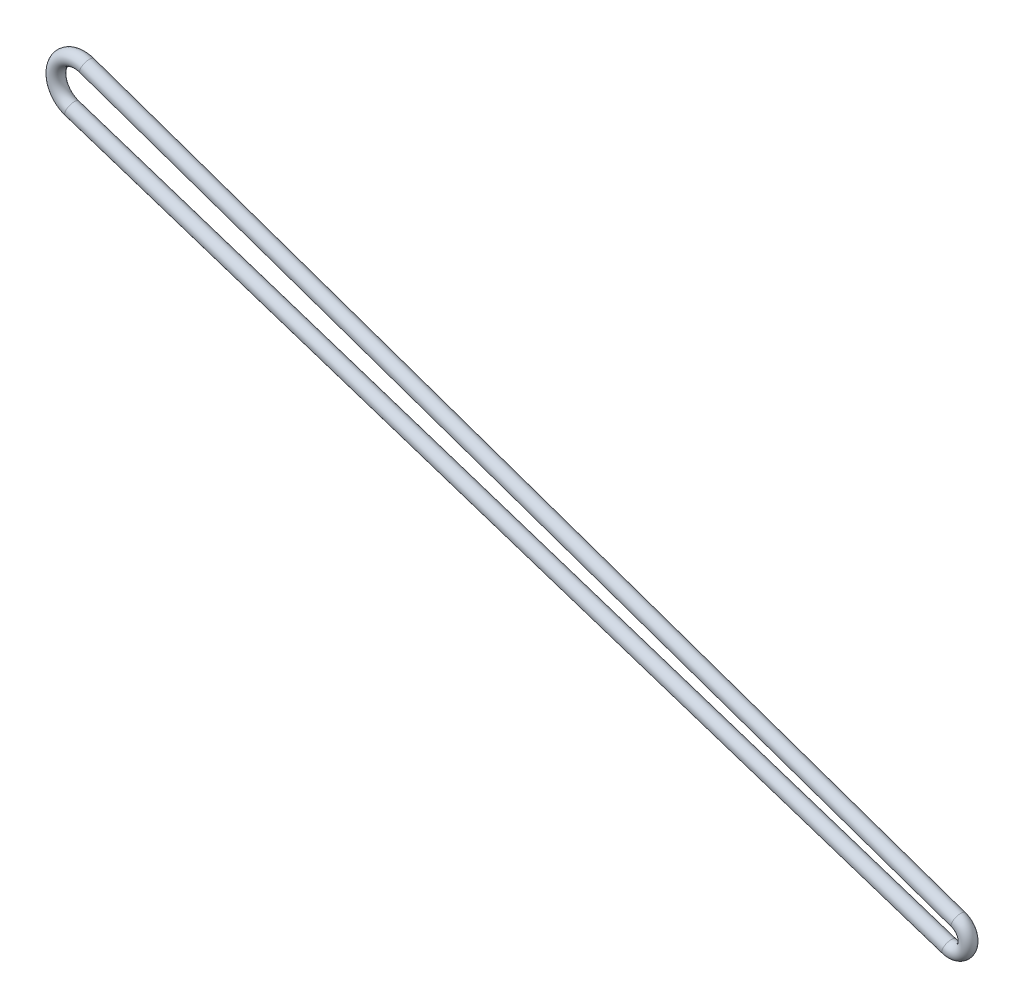
SolidWorks part; units mm, degrees
ref_plane "前视基准面" through (0, 0, 0) normal (0, 0, 1) x (1, 0, 0)
ref_plane "上视基准面" through (0, 0, 0) normal (0, 1, 0) x (1, 0, 0)
ref_plane "右视基准面" through (0, 0, 0) normal (1, 0, 0) x (0, 0, -1)
sketch "草图2" plane through (0, 0, 0) normal (0, 0, 1) x (1, 0, 0)
  line L0 (0, 0) -> (1, 0) construction
  line L1 (0, 0) -> (0, 1) construction
  line L2 (293.9722, 75.0424) -> (106.5181, 136.3941)
  line L3 (109.7199, 145.8671) -> (295.9573, 80.9157)
  arc A0 (295.9573, 80.9157) -> (293.9722, 75.0424) centre (294.9365, 77.9886) cw
  arc A1 (106.5181, 136.3941) -> (109.7199, 145.8671) centre (108.0733, 141.146) cw
sweep "扫描19" add path "草图2" circular profile diameter 3 parameters "D3"=3
